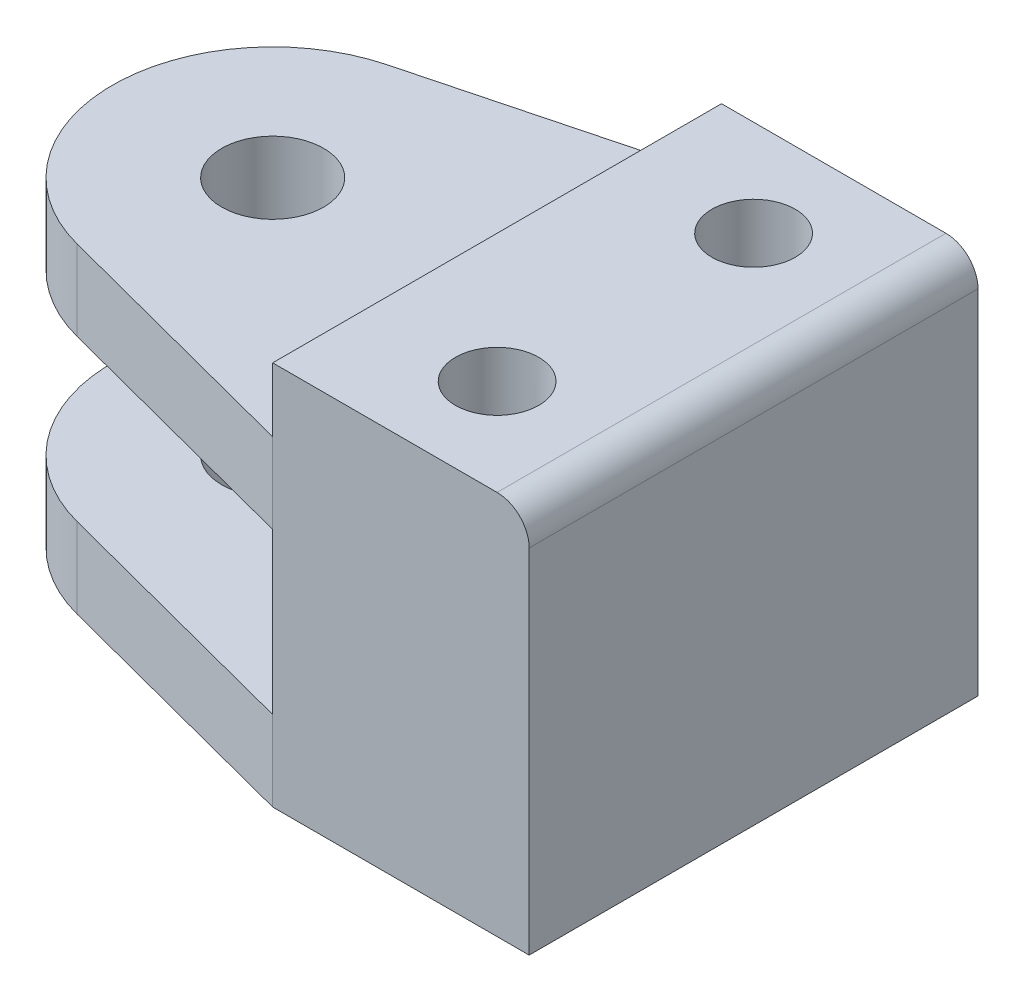
SolidWorks part; units mm, degrees
material "ABS"
ref_plane "Front Plane" through (0, 0, 0) normal (0, 0, 1) x (1, 0, 0)
ref_plane "Top Plane" through (0, 0, 0) normal (0, 1, 0) x (1, 0, 0)
ref_plane "Right Plane" through (0, 0, 0) normal (1, 0, 0) x (0, 0, -1)
sketch "Sketch1" plane through (0, 0, 0) normal (0, 1, 0) x (1, 0, 0)
  line L0 (7, 7) -> (-1.2657, 4.8371)
  line L1 (15, -7) -> (7, -7)
  line L2 (15, -7) -> (15, 7)
  line L3 (15, 7) -> (7, 7)
  line L4 (7, -7) -> (7, 7)
  line L5 (15, -7) -> (7, 7) construction
  line L6 (15, 7) -> (7, -7) construction
  line L7 (-1.2657, -4.8371) -> (7, -7)
  circle A0 centre (0, 0) radius 6.35 construction
  circle A1 centre (0, 0) radius 1.59
  arc A2 (-1.2657, 4.8371) -> (-1.2657, -4.8371) centre (0, 0) ccw
  point P0 (11, 0)
  dimension "D4" = 12.7
  dimension "D5" = 3.18
  dimension "D8" = 5
  dimension "D1" = 14
  dimension "D2" = 8
  dimension "D3" = 7
extrude "Boss-Extrude1" add sketch "Sketch1" along normal blind 7 and the other way blind 5 contours L3 L4 L1 L2
extrude "Boss-Extrude2" add sketch "Sketch1<3>" along normal blind 2.5 from offset 2.5 contours L0 A2 L7 L4 A1 region at (1.9692, 0, 0)
sketch "Sketch1<3>" plane through (0, 0, 0) normal (0, 1, 0) x (1, 0, 0) same geometry as "Sketch1"
extrude "Boss-Extrude3" add sketch "Sketch1<4>" against normal blind 2.5 from offset 2.5 contours L0 A2 L7 L4 A1 region at (1.9692, 0, 0) offset against normal yes
sketch "Sketch1<4>" plane through (0, 0, 0) normal (0, 1, 0) x (1, 0, 0) same geometry as "Sketch1"
hole_wizard "M2 Clearance Hole1" positions "Sketch2" profile "Sketch3" hole size "M2" standard "ANSI Metric" end condition through all
sketch "Sketch2" plane through (0, 7, 0) normal (0, 1, 0) x (1, 0, 0)
  line L0 (0, 0) -> (26.0483, 0) construction
  point P0 (11, 4)
  point P2 (11, -4)
  point P11 (11, 4)
  dimension "D1" = 11
  dimension "D2" = 8
sketch "Sketch3" plane through (11, 7, -4) normal (1, 0, 0) x (0, 0, 1)
  line L0 (0, 0) -> (0, 12)
  line L1 (0, 12) -> (1.3, 12)
  line L2 (1.3, 12) -> (1.3, 0)
  line L5 (1.3, 0) -> (0, 0)
  line L11 (0, -6.35) -> (0, 107.95) construction
  dimension "Thru Hole Dia." = 2.6
  dimension "Thru Hole Depth" = 12
fillet "Fillet1" [suppressed] radius 3
sketch "Sketch4" plane through (0, -5, 0) normal (0, -1, 0) x (1, 0, 0)
  line L1 (9.8164, 1.95) -> (12.1836, 1.95)
  line L2 (12.1836, 1.95) -> (13.3671, 4)
  line L3 (13.3671, 4) -> (12.1836, 6.05)
  line L4 (12.1836, 6.05) -> (9.8164, 6.05)
  line L5 (9.8164, 6.05) -> (8.6329, 4)
  line L6 (8.6329, 4) -> (9.8164, 1.95)
  line L7 (8.6329, -4) -> (9.8164, -6.05)
  line L8 (9.8164, -6.05) -> (12.1836, -6.05)
  line L9 (12.1836, -6.05) -> (13.3671, -4)
  line L10 (13.3671, -4) -> (12.1836, -1.95)
  line L11 (12.1836, -1.95) -> (9.8164, -1.95)
  line L12 (9.8164, -1.95) -> (8.6329, -4)
  circle A0 centre (11, 4) radius 2.05 construction
  circle A1 centre (11, -4) radius 2.05 construction
  dimension "D1" = 4.1
  dimension "D2" = 4.1
extrude "Cut-Extrude1" cut sketch "Sketch4" against normal blind 3
fillet "Fillet2" radius 1 1 edges at (15, 7, 0)
